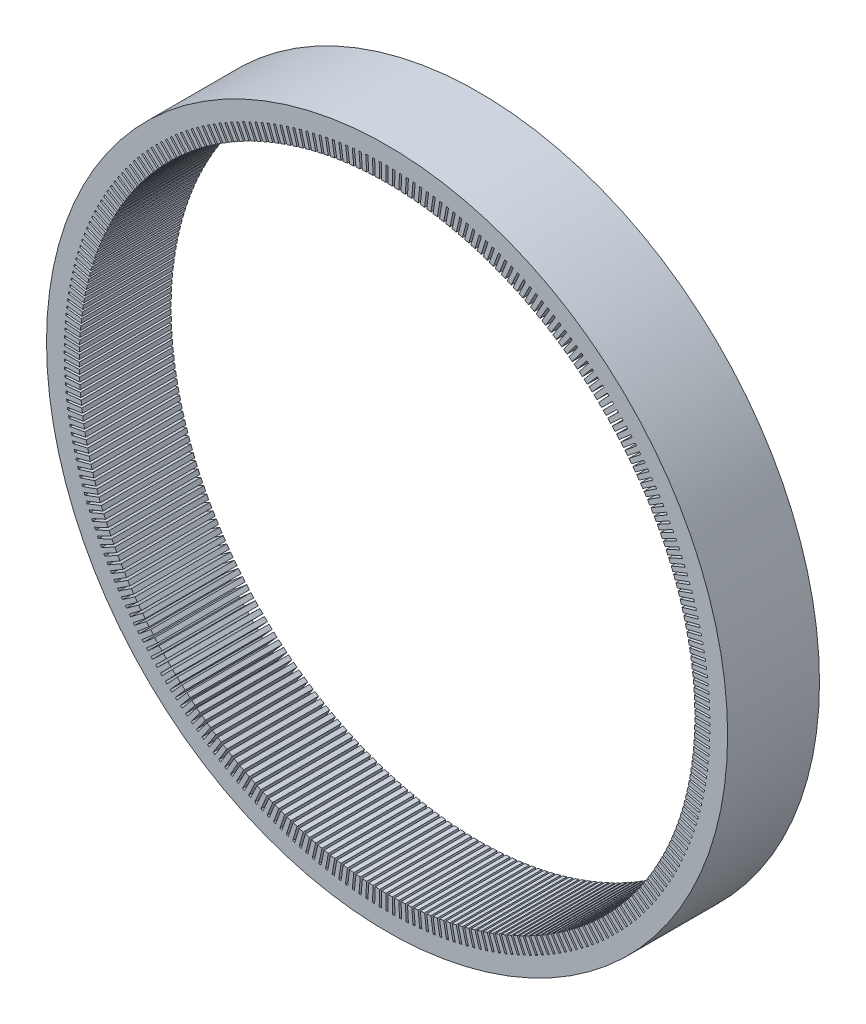
SolidWorks part; units mm, degrees
material "1023 Carbon Steel Sheet (SS)"
ref_plane "Front Plane" through (0, 0, 0) normal (0, 0, 1) x (1, 0, 0)
ref_plane "Top Plane" through (0, 0, 0) normal (0, 1, 0) x (1, 0, 0)
ref_plane "Right Plane" through (0, 0, 0) normal (1, 0, 0) x (0, 0, -1)
sketch "Sketch1" plane through (0, 0, 0) normal (0, 0, 1) x (1, 0, 0)
  line L0 (-11, 3098.7805) -> (-11, 3250.7805)
  line L1 (-11, 3250.7805) -> (11, 3250.7805)
  line L2 (11, 3250.7805) -> (11, 3098.7805)
  line L3 (57.0816, 3250.2979) -> (79.0768, 3249.8372)
  line L4 (53.8984, 3098.3312) -> (57.0816, 3250.2979)
  line L5 (79.0768, 3249.8372) -> (75.8935, 3097.8705)
  line L6 (125.1382, 3248.3896) -> (147.1189, 3247.4684)
  line L7 (118.7731, 3096.523) -> (125.1382, 3248.3896)
  line L8 (147.1189, 3247.4684) -> (140.7538, 3095.6017)
  line L9 (193.1399, 3245.0565) -> (215.0965, 3243.6751)
  line L10 (183.5957, 3093.3564) -> (193.1399, 3245.0565)
  line L11 (215.0965, 3243.6751) -> (205.5523, 3091.975)
  line L12 (261.0569, 3240.3) -> (282.9797, 3238.4591)
  line L13 (248.3378, 3088.8331) -> (261.0569, 3240.3)
  line L14 (282.9797, 3238.4591) -> (270.2607, 3086.9922)
  line L15 (328.8593, 3234.1222) -> (350.7388, 3231.8225)
  line L16 (312.971, 3082.9548) -> (328.8593, 3234.1222)
  line L17 (350.7388, 3231.8225) -> (334.8505, 3080.6552)
  line L18 (396.5176, 3226.5258) -> (418.3441, 3223.7684)
  line L19 (377.4669, 3075.7243) -> (396.5176, 3226.5258)
  line L20 (418.3441, 3223.7684) -> (399.2934, 3072.967)
  line L21 (464.0019, 3217.5141) -> (485.7659, 3214.3003)
  line L22 (441.7972, 3067.1447) -> (464.0019, 3217.5141)
  line L23 (485.7659, 3214.3003) -> (463.5612, 3063.9309)
  line L24 (531.2826, 3207.0911) -> (552.9745, 3203.4222)
  line L25 (505.9338, 3057.2197) -> (531.2826, 3207.0911)
  line L26 (552.9745, 3203.4222) -> (527.6257, 3053.5508)
  line L27 (598.3304, 3195.2614) -> (619.9407, 3191.139)
  line L28 (569.8484, 3045.9537) -> (598.3304, 3195.2614)
  line L29 (619.9407, 3191.139) -> (591.4587, 3041.8314)
  line L30 (665.1156, 3182.0302) -> (686.6349, 3177.4561)
  line L31 (633.5131, 3033.3517) -> (665.1156, 3182.0302)
  line L32 (686.6349, 3177.4561) -> (655.0323, 3028.7777)
  line L33 (731.6092, 3167.4031) -> (753.0279, 3162.3794)
  line L34 (696.8999, 3019.4192) -> (731.6092, 3167.4031)
  line L35 (753.0279, 3162.3794) -> (718.3186, 3014.3954)
  line L36 (797.7818, 3151.3868) -> (819.0906, 3145.9156)
  line L37 (759.981, 3004.1622) -> (797.7818, 3151.3868)
  line L38 (819.0906, 3145.9156) -> (781.2898, 2998.691)
  line L39 (863.6045, 3133.9882) -> (884.7941, 3128.0719)
  line L40 (822.7287, 2987.5875) -> (863.6045, 3133.9882)
  line L41 (884.7941, 3128.0719) -> (843.9183, 2981.6712)
  line L42 (929.0484, 3115.2149) -> (950.1094, 3108.8562)
  line L43 (885.1156, 2969.7023) -> (929.0484, 3115.2149)
  line L44 (950.1094, 3108.8562) -> (906.1766, 2963.3436)
  line L45 (994.0848, 3095.0751) -> (1015.008, 3088.2768)
  line L46 (947.1142, 2950.5146) -> (994.0848, 3095.0751)
  line L47 (1015.008, 3088.2768) -> (968.0375, 2943.7162)
  line L48 (1058.6851, 3073.5778) -> (1079.4614, 3066.3427)
  line L49 (1008.6974, 2930.0326) -> (1058.6851, 3073.5778)
  line L50 (1079.4614, 3066.3427) -> (1029.4737, 2922.7975)
  line L51 (1122.8211, 3050.7323) -> (1143.4413, 3043.0637)
  line L52 (1069.8382, 2908.2654) -> (1122.8211, 3050.7323)
  line L53 (1143.4413, 3043.0637) -> (1090.4584, 2900.5968)
  line L54 (1186.4646, 3026.5486) -> (1206.9197, 3018.4499)
  line L55 (1130.5096, 2885.2226) -> (1186.4646, 3026.5486)
  line L56 (1206.9197, 3018.4499) -> (1150.9647, 2877.1239)
  line L57 (1249.5876, 3001.0374) -> (1269.8686, 2992.5121)
  line L58 (1190.6852, 2860.9142) -> (1249.5876, 3001.0374)
  line L59 (1269.8686, 2992.5121) -> (1210.9662, 2852.3889)
  line L60 (1312.1625, 2974.2098) -> (1332.2605, 2965.2616)
  line L61 (1250.3386, 2835.3509) -> (1312.1625, 2974.2098)
  line L62 (1332.2605, 2965.2616) -> (1270.4366, 2826.4027)
  line L63 (1374.1619, 2946.0777) -> (1394.0681, 2936.7105)
  line L64 (1309.4435, 2808.544) -> (1374.1619, 2946.0777)
  line L65 (1394.0681, 2936.7105) -> (1329.3497, 2799.1768)
  line L66 (1435.5585, 2916.6533) -> (1455.2642, 2906.8713)
  line L67 (1367.974, 2780.5051) -> (1435.5585, 2916.6533)
  line L68 (1455.2642, 2906.8713) -> (1387.6796, 2770.7231)
  line L69 (1496.3255, 2885.9495) -> (1515.8219, 2875.757)
  line L70 (1425.9045, 2751.2466) -> (1496.3255, 2885.9495)
  line L71 (1515.8219, 2875.757) -> (1445.4009, 2741.0541)
  line L72 (1556.4361, 2853.9799) -> (1575.7148, 2843.3814)
  line L73 (1483.2095, 2720.7813) -> (1556.4361, 2853.9799)
  line L74 (1575.7148, 2843.3814) -> (1502.4883, 2710.1827)
  line L75 (1615.864, 2820.7585) -> (1634.9165, 2809.7585)
  line L76 (1539.864, 2689.1226) -> (1615.864, 2820.7585)
  line L77 (1634.9165, 2809.7585) -> (1558.9165, 2678.1226)
  line L78 (1674.5831, 2786.2997) -> (1693.4011, 2774.9031)
  line L79 (1595.843, 2656.2844) -> (1674.5831, 2786.2997)
  line L80 (1693.4011, 2774.9031) -> (1614.661, 2644.8878)
  line L81 (1732.5677, 2750.6188) -> (1751.1429, 2738.8306)
  line L82 (1651.122, 2622.281) -> (1732.5677, 2750.6188)
  line L83 (1751.1429, 2738.8306) -> (1669.6972, 2610.4928)
  line L84 (1789.7923, 2713.7314) -> (1808.1166, 2701.5568)
  line L85 (1705.6768, 2587.1274) -> (1789.7923, 2713.7314)
  line L86 (1808.1166, 2701.5568) -> (1724.0011, 2574.9528)
  line L87 (1846.2319, 2675.6537) -> (1864.2972, 2663.098)
  line L88 (1759.4834, 2550.839) -> (1846.2319, 2675.6537)
  line L89 (1864.2972, 2663.098) -> (1777.5487, 2538.2833)
  line L90 (1901.8616, 2636.4023) -> (1919.66, 2623.471)
  line L91 (1812.5183, 2513.4317) -> (1901.8616, 2636.4023)
  line L92 (1919.66, 2623.471) -> (1830.3167, 2500.5004)
  line L93 (1956.6572, 2595.9945) -> (1974.1808, 2582.6933)
  line L94 (1864.7581, 2474.9219) -> (1956.6572, 2595.9945)
  line L95 (1974.1808, 2582.6933) -> (1882.2818, 2461.6208)
  line L96 (2010.5944, 2554.448) -> (2027.8357, 2540.7828)
  line L97 (1916.18, 2435.3266) -> (2010.5944, 2554.448)
  line L98 (2027.8357, 2540.7828) -> (1933.4212, 2421.6614)
  line L99 (2063.6498, 2511.7811) -> (2080.6011, 2497.7577)
  line L100 (1966.7614, 2394.6631) -> (2063.6498, 2511.7811)
  line L101 (2080.6011, 2497.7577) -> (1983.7127, 2380.6397)
  line L102 (2115.8, 2468.0124) -> (2132.4539, 2453.6371)
  line L103 (2016.4801, 2352.9491) -> (2115.8, 2468.0124)
  line L104 (2132.4539, 2453.6371) -> (2033.134, 2338.5739)
  line L105 (2167.0221, 2423.1611) -> (2183.3713, 2408.4403)
  line L106 (2065.3143, 2310.2031) -> (2167.0221, 2423.1611)
  line L107 (2183.3713, 2408.4403) -> (2081.6635, 2295.4822)
  line L108 (2217.2937, 2377.247) -> (2233.331, 2362.187)
  line L109 (2113.2426, 2266.4438) -> (2217.2937, 2377.247)
  line L110 (2233.331, 2362.187) -> (2129.2799, 2251.3837)
  line L111 (2266.5927, 2330.2901) -> (2282.3111, 2314.8975)
  line L112 (2160.2439, 2221.6903) -> (2266.5927, 2330.2901)
  line L113 (2282.3111, 2314.8975) -> (2175.9623, 2206.2977)
  line L114 (2314.8975, 2282.3111) -> (2330.2901, 2266.5927)
  line L115 (2206.2977, 2175.9623) -> (2314.8975, 2282.3111)
  line L116 (2330.2901, 2266.5927) -> (2221.6903, 2160.2439)
  line L117 (2362.187, 2233.331) -> (2377.247, 2217.2937)
  line L118 (2251.3837, 2129.2799) -> (2362.187, 2233.331)
  line L119 (2377.247, 2217.2937) -> (2266.4438, 2113.2426)
  line L120 (2408.4403, 2183.3713) -> (2423.1611, 2167.0221)
  line L121 (2295.4822, 2081.6635) -> (2408.4403, 2183.3713)
  line L122 (2423.1611, 2167.0221) -> (2310.2031, 2065.3143)
  line L123 (2453.6371, 2132.4539) -> (2468.0124, 2115.8)
  line L124 (2338.5739, 2033.134) -> (2453.6371, 2132.4539)
  line L125 (2468.0124, 2115.8) -> (2352.9491, 2016.4801)
  line L126 (2497.7577, 2080.6011) -> (2511.7811, 2063.6498)
  line L127 (2380.6397, 1983.7127) -> (2497.7577, 2080.6011)
  line L128 (2511.7811, 2063.6498) -> (2394.6631, 1966.7614)
  line L129 (2540.7828, 2027.8357) -> (2554.448, 2010.5944)
  line L130 (2421.6614, 1933.4212) -> (2540.7828, 2027.8357)
  line L131 (2554.448, 2010.5944) -> (2435.3266, 1916.18)
  line L132 (2582.6933, 1974.1808) -> (2595.9945, 1956.6572)
  line L133 (2461.6208, 1882.2818) -> (2582.6933, 1974.1808)
  line L134 (2595.9945, 1956.6572) -> (2474.9219, 1864.7581)
  line L135 (2623.471, 1919.66) -> (2636.4023, 1901.8616)
  line L136 (2500.5004, 1830.3167) -> (2623.471, 1919.66)
  line L137 (2636.4023, 1901.8616) -> (2513.4317, 1812.5183)
  line L138 (2663.098, 1864.2972) -> (2675.6537, 1846.2319)
  line L139 (2538.2833, 1777.5487) -> (2663.098, 1864.2972)
  line L140 (2675.6537, 1846.2319) -> (2550.839, 1759.4834)
  line L141 (2701.5568, 1808.1166) -> (2713.7314, 1789.7923)
  line L142 (2574.9528, 1724.0011) -> (2701.5568, 1808.1166)
  line L143 (2713.7314, 1789.7923) -> (2587.1274, 1705.6768)
  line L144 (2738.8306, 1751.1429) -> (2750.6188, 1732.5677)
  line L145 (2610.4928, 1669.6972) -> (2738.8306, 1751.1429)
  line L146 (2750.6188, 1732.5677) -> (2622.281, 1651.122)
  line L147 (2774.9031, 1693.4011) -> (2786.2997, 1674.5831)
  line L148 (2644.8878, 1614.661) -> (2774.9031, 1693.4011)
  line L149 (2786.2997, 1674.5831) -> (2656.2844, 1595.843)
  line L150 (2809.7585, 1634.9165) -> (2820.7585, 1615.864)
  line L151 (2678.1226, 1558.9165) -> (2809.7585, 1634.9165)
  line L152 (2820.7585, 1615.864) -> (2689.1226, 1539.864)
  line L153 (2843.3814, 1575.7148) -> (2853.9799, 1556.4361)
  line L154 (2710.1827, 1502.4883) -> (2843.3814, 1575.7148)
  line L155 (2853.9799, 1556.4361) -> (2720.7813, 1483.2095)
  line L156 (2875.757, 1515.8219) -> (2885.9495, 1496.3255)
  line L157 (2741.0541, 1445.4009) -> (2875.757, 1515.8219)
  line L158 (2885.9495, 1496.3255) -> (2751.2466, 1425.9045)
  line L159 (2906.8713, 1455.2642) -> (2916.6533, 1435.5585)
  line L160 (2770.7231, 1387.6796) -> (2906.8713, 1455.2642)
  line L161 (2916.6533, 1435.5585) -> (2780.5051, 1367.974)
  line L162 (2936.7105, 1394.0681) -> (2946.0777, 1374.1619)
  line L163 (2799.1768, 1329.3497) -> (2936.7105, 1394.0681)
  line L164 (2946.0777, 1374.1619) -> (2808.544, 1309.4435)
  line L165 (2965.2616, 1332.2605) -> (2974.2098, 1312.1625)
  line L166 (2826.4027, 1270.4366) -> (2965.2616, 1332.2605)
  line L167 (2974.2098, 1312.1625) -> (2835.3509, 1250.3386)
  line L168 (2992.5121, 1269.8686) -> (3001.0374, 1249.5876)
  line L169 (2852.3889, 1210.9662) -> (2992.5121, 1269.8686)
  line L170 (3001.0374, 1249.5876) -> (2860.9142, 1190.6852)
  line L171 (3018.4499, 1206.9197) -> (3026.5486, 1186.4646)
  line L172 (2877.1239, 1150.9647) -> (3018.4499, 1206.9197)
  line L173 (3026.5486, 1186.4646) -> (2885.2226, 1130.5096)
  line L174 (3043.0637, 1143.4413) -> (3050.7323, 1122.8211)
  line L175 (2900.5968, 1090.4584) -> (3043.0637, 1143.4413)
  line L176 (3050.7323, 1122.8211) -> (2908.2654, 1069.8382)
  line L177 (3066.3427, 1079.4614) -> (3073.5778, 1058.6851)
  line L178 (2922.7975, 1029.4737) -> (3066.3427, 1079.4614)
  line L179 (3073.5778, 1058.6851) -> (2930.0326, 1008.6974)
  line L180 (3088.2768, 1015.008) -> (3095.0751, 994.0848)
  line L181 (2943.7162, 968.0375) -> (3088.2768, 1015.008)
  line L182 (3095.0751, 994.0848) -> (2950.5146, 947.1142)
  line L183 (3108.8562, 950.1094) -> (3115.2149, 929.0484)
  line L184 (2963.3436, 906.1766) -> (3108.8562, 950.1094)
  line L185 (3115.2149, 929.0484) -> (2969.7023, 885.1156)
  line L186 (3128.0719, 884.7941) -> (3133.9882, 863.6045)
  line L187 (2981.6712, 843.9183) -> (3128.0719, 884.7941)
  line L188 (3133.9882, 863.6045) -> (2987.5875, 822.7287)
  line L189 (3145.9156, 819.0906) -> (3151.3868, 797.7818)
  line L190 (2998.691, 781.2898) -> (3145.9156, 819.0906)
  line L191 (3151.3868, 797.7818) -> (3004.1622, 759.981)
  line L192 (3162.3794, 753.0279) -> (3167.4031, 731.6092)
  line L193 (3014.3954, 718.3186) -> (3162.3794, 753.0279)
  line L194 (3167.4031, 731.6092) -> (3019.4192, 696.8999)
  line L195 (3177.4561, 686.6349) -> (3182.0302, 665.1156)
  line L196 (3028.7777, 655.0323) -> (3177.4561, 686.6349)
  line L197 (3182.0302, 665.1156) -> (3033.3517, 633.5131)
  line L198 (3191.139, 619.9407) -> (3195.2614, 598.3304)
  line L199 (3041.8314, 591.4587) -> (3191.139, 619.9407)
  line L200 (3195.2614, 598.3304) -> (3045.9537, 569.8484)
  line L201 (3203.4222, 552.9745) -> (3207.0911, 531.2826)
  line L202 (3053.5508, 527.6257) -> (3203.4222, 552.9745)
  line L203 (3207.0911, 531.2826) -> (3057.2197, 505.9338)
  line L204 (3214.3003, 485.7659) -> (3217.5141, 464.0019)
  line L205 (3063.9309, 463.5612) -> (3214.3003, 485.7659)
  line L206 (3217.5141, 464.0019) -> (3067.1447, 441.7972)
  line L207 (3223.7684, 418.3441) -> (3226.5258, 396.5176)
  line L208 (3072.967, 399.2934) -> (3223.7684, 418.3441)
  line L209 (3226.5258, 396.5176) -> (3075.7243, 377.4669)
  line L210 (3231.8225, 350.7388) -> (3234.1222, 328.8593)
  line L211 (3080.6552, 334.8505) -> (3231.8225, 350.7388)
  line L212 (3234.1222, 328.8593) -> (3082.9548, 312.971)
  line L213 (3238.4591, 282.9797) -> (3240.3, 261.0569)
  line L214 (3086.9922, 270.2607) -> (3238.4591, 282.9797)
  line L215 (3240.3, 261.0569) -> (3088.8331, 248.3378)
  line L216 (3243.6751, 215.0965) -> (3245.0565, 193.1399)
  line L217 (3091.975, 205.5523) -> (3243.6751, 215.0965)
  line L218 (3245.0565, 193.1399) -> (3093.3564, 183.5957)
  line L219 (3247.4684, 147.1189) -> (3248.3896, 125.1382)
  line L220 (3095.6017, 140.7538) -> (3247.4684, 147.1189)
  line L221 (3248.3896, 125.1382) -> (3096.523, 118.7731)
  line L222 (3249.8372, 79.0768) -> (3250.2979, 57.0816)
  line L223 (3097.8705, 75.8935) -> (3249.8372, 79.0768)
  line L224 (3250.2979, 57.0816) -> (3098.3312, 53.8984)
  line L225 (3250.7805, 11) -> (3250.7805, -11)
  line L226 (3098.7805, 11) -> (3250.7805, 11)
  line L227 (3250.7805, -11) -> (3098.7805, -11)
  line L228 (3250.2979, -57.0816) -> (3249.8372, -79.0768)
  line L229 (3098.3312, -53.8984) -> (3250.2979, -57.0816)
  line L230 (3249.8372, -79.0768) -> (3097.8705, -75.8935)
  line L231 (3248.3896, -125.1382) -> (3247.4684, -147.1189)
  line L232 (3096.523, -118.7731) -> (3248.3896, -125.1382)
  line L233 (3247.4684, -147.1189) -> (3095.6017, -140.7538)
  line L234 (3245.0565, -193.1399) -> (3243.6751, -215.0965)
  line L235 (3093.3564, -183.5957) -> (3245.0565, -193.1399)
  line L236 (3243.6751, -215.0965) -> (3091.975, -205.5523)
  line L237 (3240.3, -261.0569) -> (3238.4591, -282.9797)
  line L238 (3088.8331, -248.3378) -> (3240.3, -261.0569)
  line L239 (3238.4591, -282.9797) -> (3086.9922, -270.2607)
  line L240 (3234.1222, -328.8593) -> (3231.8225, -350.7388)
  line L241 (3082.9548, -312.971) -> (3234.1222, -328.8593)
  line L242 (3231.8225, -350.7388) -> (3080.6552, -334.8505)
  line L243 (3226.5258, -396.5176) -> (3223.7684, -418.3441)
  line L244 (3075.7243, -377.4669) -> (3226.5258, -396.5176)
  line L245 (3223.7684, -418.3441) -> (3072.967, -399.2934)
  line L246 (3217.5141, -464.0019) -> (3214.3003, -485.7659)
  line L247 (3067.1447, -441.7972) -> (3217.5141, -464.0019)
  line L248 (3214.3003, -485.7659) -> (3063.9309, -463.5612)
  line L249 (3207.0911, -531.2826) -> (3203.4222, -552.9745)
  line L250 (3057.2197, -505.9338) -> (3207.0911, -531.2826)
  line L251 (3203.4222, -552.9745) -> (3053.5508, -527.6257)
  line L252 (3195.2614, -598.3304) -> (3191.139, -619.9407)
  line L253 (3045.9537, -569.8484) -> (3195.2614, -598.3304)
  line L254 (3191.139, -619.9407) -> (3041.8314, -591.4587)
  line L255 (3182.0302, -665.1156) -> (3177.4561, -686.6349)
  line L256 (3033.3517, -633.5131) -> (3182.0302, -665.1156)
  line L257 (3177.4561, -686.6349) -> (3028.7777, -655.0323)
  line L258 (3167.4031, -731.6092) -> (3162.3794, -753.0279)
  line L259 (3019.4192, -696.8999) -> (3167.4031, -731.6092)
  line L260 (3162.3794, -753.0279) -> (3014.3954, -718.3186)
  line L261 (3151.3868, -797.7818) -> (3145.9156, -819.0906)
  line L262 (3004.1622, -759.981) -> (3151.3868, -797.7818)
  line L263 (3145.9156, -819.0906) -> (2998.691, -781.2898)
  line L264 (3133.9882, -863.6045) -> (3128.0719, -884.7941)
  line L265 (2987.5875, -822.7287) -> (3133.9882, -863.6045)
  line L266 (3128.0719, -884.7941) -> (2981.6712, -843.9183)
  line L267 (3115.2149, -929.0484) -> (3108.8562, -950.1094)
  line L268 (2969.7023, -885.1156) -> (3115.2149, -929.0484)
  line L269 (3108.8562, -950.1094) -> (2963.3436, -906.1766)
  line L270 (3095.0751, -994.0848) -> (3088.2768, -1015.008)
  line L271 (2950.5146, -947.1142) -> (3095.0751, -994.0848)
  line L272 (3088.2768, -1015.008) -> (2943.7162, -968.0375)
  line L273 (3073.5778, -1058.6851) -> (3066.3427, -1079.4614)
  line L274 (2930.0326, -1008.6974) -> (3073.5778, -1058.6851)
  line L275 (3066.3427, -1079.4614) -> (2922.7975, -1029.4737)
  line L276 (3050.7323, -1122.8211) -> (3043.0637, -1143.4413)
  line L277 (2908.2654, -1069.8382) -> (3050.7323, -1122.8211)
  line L278 (3043.0637, -1143.4413) -> (2900.5968, -1090.4584)
  line L279 (3026.5486, -1186.4646) -> (3018.4499, -1206.9197)
  line L280 (2885.2226, -1130.5096) -> (3026.5486, -1186.4646)
  line L281 (3018.4499, -1206.9197) -> (2877.1239, -1150.9647)
  line L282 (3001.0374, -1249.5876) -> (2992.5121, -1269.8686)
  line L283 (2860.9142, -1190.6852) -> (3001.0374, -1249.5876)
  line L284 (2992.5121, -1269.8686) -> (2852.3889, -1210.9662)
  line L285 (2974.2098, -1312.1625) -> (2965.2616, -1332.2605)
  line L286 (2835.3509, -1250.3386) -> (2974.2098, -1312.1625)
  line L287 (2965.2616, -1332.2605) -> (2826.4027, -1270.4366)
  line L288 (2946.0777, -1374.1619) -> (2936.7105, -1394.0681)
  line L289 (2808.544, -1309.4435) -> (2946.0777, -1374.1619)
  line L290 (2936.7105, -1394.0681) -> (2799.1768, -1329.3497)
  line L291 (2916.6533, -1435.5585) -> (2906.8713, -1455.2642)
  line L292 (2780.5051, -1367.974) -> (2916.6533, -1435.5585)
  line L293 (2906.8713, -1455.2642) -> (2770.7231, -1387.6796)
  line L294 (2885.9495, -1496.3255) -> (2875.757, -1515.8219)
  line L295 (2751.2466, -1425.9045) -> (2885.9495, -1496.3255)
  line L296 (2875.757, -1515.8219) -> (2741.0541, -1445.4009)
  line L297 (2853.9799, -1556.4361) -> (2843.3814, -1575.7148)
  line L298 (2720.7813, -1483.2095) -> (2853.9799, -1556.4361)
  line L299 (2843.3814, -1575.7148) -> (2710.1827, -1502.4883)
  line L300 (2820.7585, -1615.864) -> (2809.7585, -1634.9165)
  line L301 (2689.1226, -1539.864) -> (2820.7585, -1615.864)
  line L302 (2809.7585, -1634.9165) -> (2678.1226, -1558.9165)
  line L303 (2786.2997, -1674.5831) -> (2774.9031, -1693.4011)
  line L304 (2656.2844, -1595.843) -> (2786.2997, -1674.5831)
  line L305 (2774.9031, -1693.4011) -> (2644.8878, -1614.661)
  line L306 (2750.6188, -1732.5677) -> (2738.8306, -1751.1429)
  line L307 (2622.281, -1651.122) -> (2750.6188, -1732.5677)
  line L308 (2738.8306, -1751.1429) -> (2610.4928, -1669.6972)
  line L309 (2713.7314, -1789.7923) -> (2701.5568, -1808.1166)
  line L310 (2587.1274, -1705.6768) -> (2713.7314, -1789.7923)
  line L311 (2701.5568, -1808.1166) -> (2574.9528, -1724.0011)
  line L312 (2675.6537, -1846.2319) -> (2663.098, -1864.2972)
  line L313 (2550.839, -1759.4834) -> (2675.6537, -1846.2319)
  line L314 (2663.098, -1864.2972) -> (2538.2833, -1777.5487)
  line L315 (2636.4023, -1901.8616) -> (2623.471, -1919.66)
  line L316 (2513.4317, -1812.5183) -> (2636.4023, -1901.8616)
  line L317 (2623.471, -1919.66) -> (2500.5004, -1830.3167)
  line L318 (2595.9945, -1956.6572) -> (2582.6933, -1974.1808)
  line L319 (2474.9219, -1864.7581) -> (2595.9945, -1956.6572)
  line L320 (2582.6933, -1974.1808) -> (2461.6208, -1882.2818)
  line L321 (2554.448, -2010.5944) -> (2540.7828, -2027.8357)
  line L322 (2435.3266, -1916.18) -> (2554.448, -2010.5944)
  line L323 (2540.7828, -2027.8357) -> (2421.6614, -1933.4212)
  line L324 (2511.7811, -2063.6498) -> (2497.7577, -2080.6011)
  line L325 (2394.6631, -1966.7614) -> (2511.7811, -2063.6498)
  line L326 (2497.7577, -2080.6011) -> (2380.6397, -1983.7127)
  line L327 (2468.0124, -2115.8) -> (2453.6371, -2132.4539)
  line L328 (2352.9491, -2016.4801) -> (2468.0124, -2115.8)
  line L329 (2453.6371, -2132.4539) -> (2338.5739, -2033.134)
  line L330 (2423.1611, -2167.0221) -> (2408.4403, -2183.3713)
  line L331 (2310.2031, -2065.3143) -> (2423.1611, -2167.0221)
  line L332 (2408.4403, -2183.3713) -> (2295.4822, -2081.6635)
  line L333 (2377.247, -2217.2937) -> (2362.187, -2233.331)
  line L334 (2266.4438, -2113.2426) -> (2377.247, -2217.2937)
  line L335 (2362.187, -2233.331) -> (2251.3837, -2129.2799)
  line L336 (2330.2901, -2266.5927) -> (2314.8975, -2282.3111)
  line L337 (2221.6903, -2160.2439) -> (2330.2901, -2266.5927)
  line L338 (2314.8975, -2282.3111) -> (2206.2977, -2175.9623)
  line L339 (2282.3111, -2314.8975) -> (2266.5927, -2330.2901)
  line L340 (2175.9623, -2206.2977) -> (2282.3111, -2314.8975)
  line L341 (2266.5927, -2330.2901) -> (2160.2439, -2221.6903)
  line L342 (2233.331, -2362.187) -> (2217.2937, -2377.247)
  line L343 (2129.2799, -2251.3837) -> (2233.331, -2362.187)
  line L344 (2217.2937, -2377.247) -> (2113.2426, -2266.4438)
  line L345 (2183.3713, -2408.4403) -> (2167.0221, -2423.1611)
  line L346 (2081.6635, -2295.4822) -> (2183.3713, -2408.4403)
  line L347 (2167.0221, -2423.1611) -> (2065.3143, -2310.2031)
  line L348 (2132.4539, -2453.6371) -> (2115.8, -2468.0124)
  line L349 (2033.134, -2338.5739) -> (2132.4539, -2453.6371)
  line L350 (2115.8, -2468.0124) -> (2016.4801, -2352.9491)
  line L351 (2080.6011, -2497.7577) -> (2063.6498, -2511.7811)
  line L352 (1983.7127, -2380.6397) -> (2080.6011, -2497.7577)
  line L353 (2063.6498, -2511.7811) -> (1966.7614, -2394.6631)
  line L354 (2027.8357, -2540.7828) -> (2010.5944, -2554.448)
  line L355 (1933.4212, -2421.6614) -> (2027.8357, -2540.7828)
  line L356 (2010.5944, -2554.448) -> (1916.18, -2435.3266)
  line L357 (1974.1808, -2582.6933) -> (1956.6572, -2595.9945)
  line L358 (1882.2818, -2461.6208) -> (1974.1808, -2582.6933)
  line L359 (1956.6572, -2595.9945) -> (1864.7581, -2474.9219)
  line L360 (1919.66, -2623.471) -> (1901.8616, -2636.4023)
  line L361 (1830.3167, -2500.5004) -> (1919.66, -2623.471)
  line L362 (1901.8616, -2636.4023) -> (1812.5183, -2513.4317)
  line L363 (1864.2972, -2663.098) -> (1846.2319, -2675.6537)
  line L364 (1777.5487, -2538.2833) -> (1864.2972, -2663.098)
  line L365 (1846.2319, -2675.6537) -> (1759.4834, -2550.839)
  line L366 (1808.1166, -2701.5568) -> (1789.7923, -2713.7314)
  line L367 (1724.0011, -2574.9528) -> (1808.1166, -2701.5568)
  line L368 (1789.7923, -2713.7314) -> (1705.6768, -2587.1274)
  line L369 (1751.1429, -2738.8306) -> (1732.5677, -2750.6188)
  line L370 (1669.6972, -2610.4928) -> (1751.1429, -2738.8306)
  line L371 (1732.5677, -2750.6188) -> (1651.122, -2622.281)
  line L372 (1693.4011, -2774.9031) -> (1674.5831, -2786.2997)
  line L373 (1614.661, -2644.8878) -> (1693.4011, -2774.9031)
  line L374 (1674.5831, -2786.2997) -> (1595.843, -2656.2844)
  line L375 (1634.9165, -2809.7585) -> (1615.864, -2820.7585)
  line L376 (1558.9165, -2678.1226) -> (1634.9165, -2809.7585)
  line L377 (1615.864, -2820.7585) -> (1539.864, -2689.1226)
  line L378 (1575.7148, -2843.3814) -> (1556.4361, -2853.9799)
  line L379 (1502.4883, -2710.1827) -> (1575.7148, -2843.3814)
  line L380 (1556.4361, -2853.9799) -> (1483.2095, -2720.7813)
  line L381 (1515.8219, -2875.757) -> (1496.3255, -2885.9495)
  line L382 (1445.4009, -2741.0541) -> (1515.8219, -2875.757)
  line L383 (1496.3255, -2885.9495) -> (1425.9045, -2751.2466)
  line L384 (1455.2642, -2906.8713) -> (1435.5585, -2916.6533)
  line L385 (1387.6796, -2770.7231) -> (1455.2642, -2906.8713)
  line L386 (1435.5585, -2916.6533) -> (1367.974, -2780.5051)
  line L387 (1394.0681, -2936.7105) -> (1374.1619, -2946.0777)
  line L388 (1329.3497, -2799.1768) -> (1394.0681, -2936.7105)
  line L389 (1374.1619, -2946.0777) -> (1309.4435, -2808.544)
  line L390 (1332.2605, -2965.2616) -> (1312.1625, -2974.2098)
  line L391 (1270.4366, -2826.4027) -> (1332.2605, -2965.2616)
  line L392 (1312.1625, -2974.2098) -> (1250.3386, -2835.3509)
  line L393 (1269.8686, -2992.5121) -> (1249.5876, -3001.0374)
  line L394 (1210.9662, -2852.3889) -> (1269.8686, -2992.5121)
  line L395 (1249.5876, -3001.0374) -> (1190.6852, -2860.9142)
  line L396 (1206.9197, -3018.4499) -> (1186.4646, -3026.5486)
  line L397 (1150.9647, -2877.1239) -> (1206.9197, -3018.4499)
  line L398 (1186.4646, -3026.5486) -> (1130.5096, -2885.2226)
  line L399 (1143.4413, -3043.0637) -> (1122.8211, -3050.7323)
  line L400 (1090.4584, -2900.5968) -> (1143.4413, -3043.0637)
  line L401 (1122.8211, -3050.7323) -> (1069.8382, -2908.2654)
  line L402 (1079.4614, -3066.3427) -> (1058.6851, -3073.5778)
  line L403 (1029.4737, -2922.7975) -> (1079.4614, -3066.3427)
  line L404 (1058.6851, -3073.5778) -> (1008.6974, -2930.0326)
  line L405 (1015.008, -3088.2768) -> (994.0848, -3095.0751)
  line L406 (968.0375, -2943.7162) -> (1015.008, -3088.2768)
  line L407 (994.0848, -3095.0751) -> (947.1142, -2950.5146)
  line L408 (950.1094, -3108.8562) -> (929.0484, -3115.2149)
  line L409 (906.1766, -2963.3436) -> (950.1094, -3108.8562)
  line L410 (929.0484, -3115.2149) -> (885.1156, -2969.7023)
  line L411 (884.7941, -3128.0719) -> (863.6045, -3133.9882)
  line L412 (843.9183, -2981.6712) -> (884.7941, -3128.0719)
  line L413 (863.6045, -3133.9882) -> (822.7287, -2987.5875)
  line L414 (819.0906, -3145.9156) -> (797.7818, -3151.3868)
  line L415 (781.2898, -2998.691) -> (819.0906, -3145.9156)
  line L416 (797.7818, -3151.3868) -> (759.981, -3004.1622)
  line L417 (753.0279, -3162.3794) -> (731.6092, -3167.4031)
  line L418 (718.3186, -3014.3954) -> (753.0279, -3162.3794)
  line L419 (731.6092, -3167.4031) -> (696.8999, -3019.4192)
  line L420 (686.6349, -3177.4561) -> (665.1156, -3182.0302)
  line L421 (655.0323, -3028.7777) -> (686.6349, -3177.4561)
  line L422 (665.1156, -3182.0302) -> (633.5131, -3033.3517)
  line L423 (619.9407, -3191.139) -> (598.3304, -3195.2614)
  line L424 (591.4587, -3041.8314) -> (619.9407, -3191.139)
  line L425 (598.3304, -3195.2614) -> (569.8484, -3045.9537)
  line L426 (552.9745, -3203.4222) -> (531.2826, -3207.0911)
  line L427 (527.6257, -3053.5508) -> (552.9745, -3203.4222)
  line L428 (531.2826, -3207.0911) -> (505.9338, -3057.2197)
  line L429 (485.7659, -3214.3003) -> (464.0019, -3217.5141)
  line L430 (463.5612, -3063.9309) -> (485.7659, -3214.3003)
  line L431 (464.0019, -3217.5141) -> (441.7972, -3067.1447)
  line L432 (418.3441, -3223.7684) -> (396.5176, -3226.5258)
  line L433 (399.2934, -3072.967) -> (418.3441, -3223.7684)
  line L434 (396.5176, -3226.5258) -> (377.4669, -3075.7243)
  line L435 (350.7388, -3231.8225) -> (328.8593, -3234.1222)
  line L436 (334.8505, -3080.6552) -> (350.7388, -3231.8225)
  line L437 (328.8593, -3234.1222) -> (312.971, -3082.9548)
  line L438 (282.9797, -3238.4591) -> (261.0569, -3240.3)
  line L439 (270.2607, -3086.9922) -> (282.9797, -3238.4591)
  line L440 (261.0569, -3240.3) -> (248.3378, -3088.8331)
  line L441 (215.0965, -3243.6751) -> (193.1399, -3245.0565)
  line L442 (205.5523, -3091.975) -> (215.0965, -3243.6751)
  line L443 (193.1399, -3245.0565) -> (183.5957, -3093.3564)
  line L444 (147.1189, -3247.4684) -> (125.1382, -3248.3896)
  line L445 (140.7538, -3095.6017) -> (147.1189, -3247.4684)
  line L446 (125.1382, -3248.3896) -> (118.7731, -3096.523)
  line L447 (79.0768, -3249.8372) -> (57.0816, -3250.2979)
  line L448 (75.8935, -3097.8705) -> (79.0768, -3249.8372)
  line L449 (57.0816, -3250.2979) -> (53.8984, -3098.3312)
  line L450 (11, -3250.7805) -> (-11, -3250.7805)
  line L451 (11, -3098.7805) -> (11, -3250.7805)
  line L452 (-11, -3250.7805) -> (-11, -3098.7805)
  line L453 (-57.0816, -3250.2979) -> (-79.0768, -3249.8372)
  line L454 (-53.8984, -3098.3312) -> (-57.0816, -3250.2979)
  line L455 (-79.0768, -3249.8372) -> (-75.8935, -3097.8705)
  line L456 (-125.1382, -3248.3896) -> (-147.1189, -3247.4684)
  line L457 (-118.7731, -3096.523) -> (-125.1382, -3248.3896)
  line L458 (-147.1189, -3247.4684) -> (-140.7538, -3095.6017)
  line L459 (-193.1399, -3245.0565) -> (-215.0965, -3243.6751)
  line L460 (-183.5957, -3093.3564) -> (-193.1399, -3245.0565)
  line L461 (-215.0965, -3243.6751) -> (-205.5523, -3091.975)
  line L462 (-261.0569, -3240.3) -> (-282.9797, -3238.4591)
  line L463 (-248.3378, -3088.8331) -> (-261.0569, -3240.3)
  line L464 (-282.9797, -3238.4591) -> (-270.2607, -3086.9922)
  line L465 (-328.8593, -3234.1222) -> (-350.7388, -3231.8225)
  line L466 (-312.971, -3082.9548) -> (-328.8593, -3234.1222)
  line L467 (-350.7388, -3231.8225) -> (-334.8505, -3080.6552)
  line L468 (-396.5176, -3226.5258) -> (-418.3441, -3223.7684)
  line L469 (-377.4669, -3075.7243) -> (-396.5176, -3226.5258)
  line L470 (-418.3441, -3223.7684) -> (-399.2934, -3072.967)
  line L471 (-464.0019, -3217.5141) -> (-485.7659, -3214.3003)
  line L472 (-441.7972, -3067.1447) -> (-464.0019, -3217.5141)
  line L473 (-485.7659, -3214.3003) -> (-463.5612, -3063.9309)
  line L474 (-531.2826, -3207.0911) -> (-552.9745, -3203.4222)
  line L475 (-505.9338, -3057.2197) -> (-531.2826, -3207.0911)
  line L476 (-552.9745, -3203.4222) -> (-527.6257, -3053.5508)
  line L477 (-598.3304, -3195.2614) -> (-619.9407, -3191.139)
  line L478 (-569.8484, -3045.9537) -> (-598.3304, -3195.2614)
  line L479 (-619.9407, -3191.139) -> (-591.4587, -3041.8314)
  line L480 (-665.1156, -3182.0302) -> (-686.6349, -3177.4561)
  line L481 (-633.5131, -3033.3517) -> (-665.1156, -3182.0302)
  line L482 (-686.6349, -3177.4561) -> (-655.0323, -3028.7777)
  line L483 (-731.6092, -3167.4031) -> (-753.0279, -3162.3794)
  line L484 (-696.8999, -3019.4192) -> (-731.6092, -3167.4031)
  line L485 (-753.0279, -3162.3794) -> (-718.3186, -3014.3954)
  line L486 (-797.7818, -3151.3868) -> (-819.0906, -3145.9156)
  line L487 (-759.981, -3004.1622) -> (-797.7818, -3151.3868)
  line L488 (-819.0906, -3145.9156) -> (-781.2898, -2998.691)
  line L489 (-863.6045, -3133.9882) -> (-884.7941, -3128.0719)
  line L490 (-822.7287, -2987.5875) -> (-863.6045, -3133.9882)
  line L491 (-884.7941, -3128.0719) -> (-843.9183, -2981.6712)
  line L492 (-929.0484, -3115.2149) -> (-950.1094, -3108.8562)
  line L493 (-885.1156, -2969.7023) -> (-929.0484, -3115.2149)
  line L494 (-950.1094, -3108.8562) -> (-906.1766, -2963.3436)
  line L495 (-994.0848, -3095.0751) -> (-1015.008, -3088.2768)
  line L496 (-947.1142, -2950.5146) -> (-994.0848, -3095.0751)
  line L497 (-1015.008, -3088.2768) -> (-968.0375, -2943.7162)
  line L498 (-1058.6851, -3073.5778) -> (-1079.4614, -3066.3427)
  line L499 (-1008.6974, -2930.0326) -> (-1058.6851, -3073.5778)
  line L500 (-1079.4614, -3066.3427) -> (-1029.4737, -2922.7975)
  line L501 (-1122.8211, -3050.7323) -> (-1143.4413, -3043.0637)
  line L502 (-1069.8382, -2908.2654) -> (-1122.8211, -3050.7323)
  line L503 (-1143.4413, -3043.0637) -> (-1090.4584, -2900.5968)
  line L504 (-1186.4646, -3026.5486) -> (-1206.9197, -3018.4499)
  line L505 (-1130.5096, -2885.2226) -> (-1186.4646, -3026.5486)
  line L506 (-1206.9197, -3018.4499) -> (-1150.9647, -2877.1239)
  line L507 (-1249.5876, -3001.0374) -> (-1269.8686, -2992.5121)
  line L508 (-1190.6852, -2860.9142) -> (-1249.5876, -3001.0374)
  line L509 (-1269.8686, -2992.5121) -> (-1210.9662, -2852.3889)
  line L510 (-1312.1625, -2974.2098) -> (-1332.2605, -2965.2616)
  line L511 (-1250.3386, -2835.3509) -> (-1312.1625, -2974.2098)
  line L512 (-1332.2605, -2965.2616) -> (-1270.4366, -2826.4027)
  line L513 (-1374.1619, -2946.0777) -> (-1394.0681, -2936.7105)
  line L514 (-1309.4435, -2808.544) -> (-1374.1619, -2946.0777)
  line L515 (-1394.0681, -2936.7105) -> (-1329.3497, -2799.1768)
  line L516 (-1435.5585, -2916.6533) -> (-1455.2642, -2906.8713)
  line L517 (-1367.974, -2780.5051) -> (-1435.5585, -2916.6533)
  line L518 (-1455.2642, -2906.8713) -> (-1387.6796, -2770.7231)
  line L519 (-1496.3255, -2885.9495) -> (-1515.8219, -2875.757)
  line L520 (-1425.9045, -2751.2466) -> (-1496.3255, -2885.9495)
  line L521 (-1515.8219, -2875.757) -> (-1445.4009, -2741.0541)
  line L522 (-1556.4361, -2853.9799) -> (-1575.7148, -2843.3814)
  line L523 (-1483.2095, -2720.7813) -> (-1556.4361, -2853.9799)
  line L524 (-1575.7148, -2843.3814) -> (-1502.4883, -2710.1827)
  line L525 (-1615.864, -2820.7585) -> (-1634.9165, -2809.7585)
  line L526 (-1539.864, -2689.1226) -> (-1615.864, -2820.7585)
  line L527 (-1634.9165, -2809.7585) -> (-1558.9165, -2678.1226)
  line L528 (-1674.5831, -2786.2997) -> (-1693.4011, -2774.9031)
  line L529 (-1595.843, -2656.2844) -> (-1674.5831, -2786.2997)
  line L530 (-1693.4011, -2774.9031) -> (-1614.661, -2644.8878)
  line L531 (-1732.5677, -2750.6188) -> (-1751.1429, -2738.8306)
  line L532 (-1651.122, -2622.281) -> (-1732.5677, -2750.6188)
  line L533 (-1751.1429, -2738.8306) -> (-1669.6972, -2610.4928)
  line L534 (-1789.7923, -2713.7314) -> (-1808.1166, -2701.5568)
  line L535 (-1705.6768, -2587.1274) -> (-1789.7923, -2713.7314)
  line L536 (-1808.1166, -2701.5568) -> (-1724.0011, -2574.9528)
  line L537 (-1846.2319, -2675.6537) -> (-1864.2972, -2663.098)
  line L538 (-1759.4834, -2550.839) -> (-1846.2319, -2675.6537)
  line L539 (-1864.2972, -2663.098) -> (-1777.5487, -2538.2833)
  line L540 (-1901.8616, -2636.4023) -> (-1919.66, -2623.471)
  line L541 (-1812.5183, -2513.4317) -> (-1901.8616, -2636.4023)
  line L542 (-1919.66, -2623.471) -> (-1830.3167, -2500.5004)
  line L543 (-1956.6572, -2595.9945) -> (-1974.1808, -2582.6933)
  line L544 (-1864.7581, -2474.9219) -> (-1956.6572, -2595.9945)
  line L545 (-1974.1808, -2582.6933) -> (-1882.2818, -2461.6208)
  line L546 (-2010.5944, -2554.448) -> (-2027.8357, -2540.7828)
  line L547 (-1916.18, -2435.3266) -> (-2010.5944, -2554.448)
  line L548 (-2027.8357, -2540.7828) -> (-1933.4212, -2421.6614)
  line L549 (-2063.6498, -2511.7811) -> (-2080.6011, -2497.7577)
  line L550 (-1966.7614, -2394.6631) -> (-2063.6498, -2511.7811)
  line L551 (-2080.6011, -2497.7577) -> (-1983.7127, -2380.6397)
  line L552 (-2115.8, -2468.0124) -> (-2132.4539, -2453.6371)
  line L553 (-2016.4801, -2352.9491) -> (-2115.8, -2468.0124)
  line L554 (-2132.4539, -2453.6371) -> (-2033.134, -2338.5739)
  line L555 (-2167.0221, -2423.1611) -> (-2183.3713, -2408.4403)
  line L556 (-2065.3143, -2310.2031) -> (-2167.0221, -2423.1611)
  line L557 (-2183.3713, -2408.4403) -> (-2081.6635, -2295.4822)
  line L558 (-2217.2937, -2377.247) -> (-2233.331, -2362.187)
  line L559 (-2113.2426, -2266.4438) -> (-2217.2937, -2377.247)
  line L560 (-2233.331, -2362.187) -> (-2129.2799, -2251.3837)
  line L561 (-2266.5927, -2330.2901) -> (-2282.3111, -2314.8975)
  line L562 (-2160.2439, -2221.6903) -> (-2266.5927, -2330.2901)
  line L563 (-2282.3111, -2314.8975) -> (-2175.9623, -2206.2977)
  line L564 (-2314.8975, -2282.3111) -> (-2330.2901, -2266.5927)
  line L565 (-2206.2977, -2175.9623) -> (-2314.8975, -2282.3111)
  line L566 (-2330.2901, -2266.5927) -> (-2221.6903, -2160.2439)
  line L567 (-2362.187, -2233.331) -> (-2377.247, -2217.2937)
  line L568 (-2251.3837, -2129.2799) -> (-2362.187, -2233.331)
  line L569 (-2377.247, -2217.2937) -> (-2266.4438, -2113.2426)
  line L570 (-2408.4403, -2183.3713) -> (-2423.1611, -2167.0221)
  line L571 (-2295.4822, -2081.6635) -> (-2408.4403, -2183.3713)
  line L572 (-2423.1611, -2167.0221) -> (-2310.2031, -2065.3143)
  line L573 (-2453.6371, -2132.4539) -> (-2468.0124, -2115.8)
  line L574 (-2338.5739, -2033.134) -> (-2453.6371, -2132.4539)
  line L575 (-2468.0124, -2115.8) -> (-2352.9491, -2016.4801)
  line L576 (-2497.7577, -2080.6011) -> (-2511.7811, -2063.6498)
  line L577 (-2380.6397, -1983.7127) -> (-2497.7577, -2080.6011)
  line L578 (-2511.7811, -2063.6498) -> (-2394.6631, -1966.7614)
  line L579 (-2540.7828, -2027.8357) -> (-2554.448, -2010.5944)
  line L580 (-2421.6614, -1933.4212) -> (-2540.7828, -2027.8357)
  line L581 (-2554.448, -2010.5944) -> (-2435.3266, -1916.18)
  line L582 (-2582.6933, -1974.1808) -> (-2595.9945, -1956.6572)
  line L583 (-2461.6208, -1882.2818) -> (-2582.6933, -1974.1808)
  line L584 (-2595.9945, -1956.6572) -> (-2474.9219, -1864.7581)
  line L585 (-2623.471, -1919.66) -> (-2636.4023, -1901.8616)
  line L586 (-2500.5004, -1830.3167) -> (-2623.471, -1919.66)
  line L587 (-2636.4023, -1901.8616) -> (-2513.4317, -1812.5183)
  line L588 (-2663.098, -1864.2972) -> (-2675.6537, -1846.2319)
  line L589 (-2538.2833, -1777.5487) -> (-2663.098, -1864.2972)
  line L590 (-2675.6537, -1846.2319) -> (-2550.839, -1759.4834)
  line L591 (-2701.5568, -1808.1166) -> (-2713.7314, -1789.7923)
  line L592 (-2574.9528, -1724.0011) -> (-2701.5568, -1808.1166)
  line L593 (-2713.7314, -1789.7923) -> (-2587.1274, -1705.6768)
  line L594 (-2738.8306, -1751.1429) -> (-2750.6188, -1732.5677)
  line L595 (-2610.4928, -1669.6972) -> (-2738.8306, -1751.1429)
  line L596 (-2750.6188, -1732.5677) -> (-2622.281, -1651.122)
  line L597 (-2774.9031, -1693.4011) -> (-2786.2997, -1674.5831)
  line L598 (-2644.8878, -1614.661) -> (-2774.9031, -1693.4011)
  line L599 (-2786.2997, -1674.5831) -> (-2656.2844, -1595.843)
  line L600 (-2809.7585, -1634.9165) -> (-2820.7585, -1615.864)
  line L601 (-2678.1226, -1558.9165) -> (-2809.7585, -1634.9165)
  line L602 (-2820.7585, -1615.864) -> (-2689.1226, -1539.864)
  line L603 (-2843.3814, -1575.7148) -> (-2853.9799, -1556.4361)
  line L604 (-2710.1827, -1502.4883) -> (-2843.3814, -1575.7148)
  line L605 (-2853.9799, -1556.4361) -> (-2720.7813, -1483.2095)
  line L606 (-2875.757, -1515.8219) -> (-2885.9495, -1496.3255)
  line L607 (-2741.0541, -1445.4009) -> (-2875.757, -1515.8219)
  line L608 (-2885.9495, -1496.3255) -> (-2751.2466, -1425.9045)
  line L609 (-2906.8713, -1455.2642) -> (-2916.6533, -1435.5585)
  line L610 (-2770.7231, -1387.6796) -> (-2906.8713, -1455.2642)
  line L611 (-2916.6533, -1435.5585) -> (-2780.5051, -1367.974)
  line L612 (-2936.7105, -1394.0681) -> (-2946.0777, -1374.1619)
  line L613 (-2799.1768, -1329.3497) -> (-2936.7105, -1394.0681)
  line L614 (-2946.0777, -1374.1619) -> (-2808.544, -1309.4435)
  line L615 (-2965.2616, -1332.2605) -> (-2974.2098, -1312.1625)
  line L616 (-2826.4027, -1270.4366) -> (-2965.2616, -1332.2605)
  line L617 (-2974.2098, -1312.1625) -> (-2835.3509, -1250.3386)
  line L618 (-2992.5121, -1269.8686) -> (-3001.0374, -1249.5876)
  line L619 (-2852.3889, -1210.9662) -> (-2992.5121, -1269.8686)
  line L620 (-3001.0374, -1249.5876) -> (-2860.9142, -1190.6852)
  line L621 (-3018.4499, -1206.9197) -> (-3026.5486, -1186.4646)
  line L622 (-2877.1239, -1150.9647) -> (-3018.4499, -1206.9197)
  line L623 (-3026.5486, -1186.4646) -> (-2885.2226, -1130.5096)
  line L624 (-3043.0637, -1143.4413) -> (-3050.7323, -1122.8211)
  line L625 (-2900.5968, -1090.4584) -> (-3043.0637, -1143.4413)
  line L626 (-3050.7323, -1122.8211) -> (-2908.2654, -1069.8382)
  line L627 (-3066.3427, -1079.4614) -> (-3073.5778, -1058.6851)
  line L628 (-2922.7975, -1029.4737) -> (-3066.3427, -1079.4614)
  line L629 (-3073.5778, -1058.6851) -> (-2930.0326, -1008.6974)
  line L630 (-3088.2768, -1015.008) -> (-3095.0751, -994.0848)
  line L631 (-2943.7162, -968.0375) -> (-3088.2768, -1015.008)
  line L632 (-3095.0751, -994.0848) -> (-2950.5146, -947.1142)
  line L633 (-3108.8562, -950.1094) -> (-3115.2149, -929.0484)
  line L634 (-2963.3436, -906.1766) -> (-3108.8562, -950.1094)
  line L635 (-3115.2149, -929.0484) -> (-2969.7023, -885.1156)
  line L636 (-3128.0719, -884.7941) -> (-3133.9882, -863.6045)
  line L637 (-2981.6712, -843.9183) -> (-3128.0719, -884.7941)
  line L638 (-3133.9882, -863.6045) -> (-2987.5875, -822.7287)
  line L639 (-3145.9156, -819.0906) -> (-3151.3868, -797.7818)
  line L640 (-2998.691, -781.2898) -> (-3145.9156, -819.0906)
  line L641 (-3151.3868, -797.7818) -> (-3004.1622, -759.981)
  line L642 (-3162.3794, -753.0279) -> (-3167.4031, -731.6092)
  line L643 (-3014.3954, -718.3186) -> (-3162.3794, -753.0279)
  line L644 (-3167.4031, -731.6092) -> (-3019.4192, -696.8999)
  line L645 (-3177.4561, -686.6349) -> (-3182.0302, -665.1156)
  line L646 (-3028.7777, -655.0323) -> (-3177.4561, -686.6349)
  line L647 (-3182.0302, -665.1156) -> (-3033.3517, -633.5131)
  line L648 (-3191.139, -619.9407) -> (-3195.2614, -598.3304)
  line L649 (-3041.8314, -591.4587) -> (-3191.139, -619.9407)
  line L650 (-3195.2614, -598.3304) -> (-3045.9537, -569.8484)
  line L651 (-3203.4222, -552.9745) -> (-3207.0911, -531.2826)
  line L652 (-3053.5508, -527.6257) -> (-3203.4222, -552.9745)
  line L653 (-3207.0911, -531.2826) -> (-3057.2197, -505.9338)
  line L654 (-3214.3003, -485.7659) -> (-3217.5141, -464.0019)
  line L655 (-3063.9309, -463.5612) -> (-3214.3003, -485.7659)
  line L656 (-3217.5141, -464.0019) -> (-3067.1447, -441.7972)
  line L657 (-3223.7684, -418.3441) -> (-3226.5258, -396.5176)
  line L658 (-3072.967, -399.2934) -> (-3223.7684, -418.3441)
  line L659 (-3226.5258, -396.5176) -> (-3075.7243, -377.4669)
  line L660 (-3231.8225, -350.7388) -> (-3234.1222, -328.8593)
  line L661 (-3080.6552, -334.8505) -> (-3231.8225, -350.7388)
  line L662 (-3234.1222, -328.8593) -> (-3082.9548, -312.971)
  line L663 (-3238.4591, -282.9797) -> (-3240.3, -261.0569)
  line L664 (-3086.9922, -270.2607) -> (-3238.4591, -282.9797)
  line L665 (-3240.3, -261.0569) -> (-3088.8331, -248.3378)
  line L666 (-3243.6751, -215.0965) -> (-3245.0565, -193.1399)
  line L667 (-3091.975, -205.5523) -> (-3243.6751, -215.0965)
  line L668 (-3245.0565, -193.1399) -> (-3093.3564, -183.5957)
  line L669 (-3247.4684, -147.1189) -> (-3248.3896, -125.1382)
  line L670 (-3095.6017, -140.7538) -> (-3247.4684, -147.1189)
  line L671 (-3248.3896, -125.1382) -> (-3096.523, -118.7731)
  line L672 (-3249.8372, -79.0768) -> (-3250.2979, -57.0816)
  line L673 (-3097.8705, -75.8935) -> (-3249.8372, -79.0768)
  line L674 (-3250.2979, -57.0816) -> (-3098.3312, -53.8984)
  line L675 (-3250.7805, -11) -> (-3250.7805, 11)
  line L676 (-3098.7805, -11) -> (-3250.7805, -11)
  line L677 (-3250.7805, 11) -> (-3098.7805, 11)
  line L678 (-3250.2979, 57.0816) -> (-3249.8372, 79.0768)
  line L679 (-3098.3312, 53.8984) -> (-3250.2979, 57.0816)
  line L680 (-3249.8372, 79.0768) -> (-3097.8705, 75.8935)
  line L681 (-3248.3896, 125.1382) -> (-3247.4684, 147.1189)
  line L682 (-3096.523, 118.7731) -> (-3248.3896, 125.1382)
  line L683 (-3247.4684, 147.1189) -> (-3095.6017, 140.7538)
  line L684 (-3245.0565, 193.1399) -> (-3243.6751, 215.0965)
  line L685 (-3093.3564, 183.5957) -> (-3245.0565, 193.1399)
  line L686 (-3243.6751, 215.0965) -> (-3091.975, 205.5523)
  line L687 (-3240.3, 261.0569) -> (-3238.4591, 282.9797)
  line L688 (-3088.8331, 248.3378) -> (-3240.3, 261.0569)
  line L689 (-3238.4591, 282.9797) -> (-3086.9922, 270.2607)
  line L690 (-3234.1222, 328.8593) -> (-3231.8225, 350.7388)
  line L691 (-3082.9548, 312.971) -> (-3234.1222, 328.8593)
  line L692 (-3231.8225, 350.7388) -> (-3080.6552, 334.8505)
  line L693 (-3226.5258, 396.5176) -> (-3223.7684, 418.3441)
  line L694 (-3075.7243, 377.4669) -> (-3226.5258, 396.5176)
  line L695 (-3223.7684, 418.3441) -> (-3072.967, 399.2934)
  line L696 (-3217.5141, 464.0019) -> (-3214.3003, 485.7659)
  line L697 (-3067.1447, 441.7972) -> (-3217.5141, 464.0019)
  line L698 (-3214.3003, 485.7659) -> (-3063.9309, 463.5612)
  line L699 (-3207.0911, 531.2826) -> (-3203.4222, 552.9745)
  line L700 (-3057.2197, 505.9338) -> (-3207.0911, 531.2826)
  line L701 (-3203.4222, 552.9745) -> (-3053.5508, 527.6257)
  line L702 (-3195.2614, 598.3304) -> (-3191.139, 619.9407)
  line L703 (-3045.9537, 569.8484) -> (-3195.2614, 598.3304)
  line L704 (-3191.139, 619.9407) -> (-3041.8314, 591.4587)
  line L705 (-3182.0302, 665.1156) -> (-3177.4561, 686.6349)
  line L706 (-3033.3517, 633.5131) -> (-3182.0302, 665.1156)
  line L707 (-3177.4561, 686.6349) -> (-3028.7777, 655.0323)
  line L708 (-3167.4031, 731.6092) -> (-3162.3794, 753.0279)
  line L709 (-3019.4192, 696.8999) -> (-3167.4031, 731.6092)
  line L710 (-3162.3794, 753.0279) -> (-3014.3954, 718.3186)
  line L711 (-3151.3868, 797.7818) -> (-3145.9156, 819.0906)
  line L712 (-3004.1622, 759.981) -> (-3151.3868, 797.7818)
  line L713 (-3145.9156, 819.0906) -> (-2998.691, 781.2898)
  line L714 (-3133.9882, 863.6045) -> (-3128.0719, 884.7941)
  line L715 (-2987.5875, 822.7287) -> (-3133.9882, 863.6045)
  line L716 (-3128.0719, 884.7941) -> (-2981.6712, 843.9183)
  line L717 (-3115.2149, 929.0484) -> (-3108.8562, 950.1094)
  line L718 (-2969.7023, 885.1156) -> (-3115.2149, 929.0484)
  line L719 (-3108.8562, 950.1094) -> (-2963.3436, 906.1766)
  line L720 (-3095.0751, 994.0848) -> (-3088.2768, 1015.008)
  line L721 (-2950.5146, 947.1142) -> (-3095.0751, 994.0848)
  line L722 (-3088.2768, 1015.008) -> (-2943.7162, 968.0375)
  line L723 (-3073.5778, 1058.6851) -> (-3066.3427, 1079.4614)
  line L724 (-2930.0326, 1008.6974) -> (-3073.5778, 1058.6851)
  line L725 (-3066.3427, 1079.4614) -> (-2922.7975, 1029.4737)
  line L726 (-3050.7323, 1122.8211) -> (-3043.0637, 1143.4413)
  line L727 (-2908.2654, 1069.8382) -> (-3050.7323, 1122.8211)
  line L728 (-3043.0637, 1143.4413) -> (-2900.5968, 1090.4584)
  line L729 (-3026.5486, 1186.4646) -> (-3018.4499, 1206.9197)
  line L730 (-2885.2226, 1130.5096) -> (-3026.5486, 1186.4646)
  line L731 (-3018.4499, 1206.9197) -> (-2877.1239, 1150.9647)
  line L732 (-3001.0374, 1249.5876) -> (-2992.5121, 1269.8686)
  line L733 (-2860.9142, 1190.6852) -> (-3001.0374, 1249.5876)
  line L734 (-2992.5121, 1269.8686) -> (-2852.3889, 1210.9662)
  line L735 (-2974.2098, 1312.1625) -> (-2965.2616, 1332.2605)
  line L736 (-2835.3509, 1250.3386) -> (-2974.2098, 1312.1625)
  line L737 (-2965.2616, 1332.2605) -> (-2826.4027, 1270.4366)
  line L738 (-2946.0777, 1374.1619) -> (-2936.7105, 1394.0681)
  line L739 (-2808.544, 1309.4435) -> (-2946.0777, 1374.1619)
  line L740 (-2936.7105, 1394.0681) -> (-2799.1768, 1329.3497)
  line L741 (-2916.6533, 1435.5585) -> (-2906.8713, 1455.2642)
  line L742 (-2780.5051, 1367.974) -> (-2916.6533, 1435.5585)
  line L743 (-2906.8713, 1455.2642) -> (-2770.7231, 1387.6796)
  line L744 (-2885.9495, 1496.3255) -> (-2875.757, 1515.8219)
  line L745 (-2751.2466, 1425.9045) -> (-2885.9495, 1496.3255)
  line L746 (-2875.757, 1515.8219) -> (-2741.0541, 1445.4009)
  line L747 (-2853.9799, 1556.4361) -> (-2843.3814, 1575.7148)
  line L748 (-2720.7813, 1483.2095) -> (-2853.9799, 1556.4361)
  line L749 (-2843.3814, 1575.7148) -> (-2710.1827, 1502.4883)
  line L750 (-2820.7585, 1615.864) -> (-2809.7585, 1634.9165)
  line L751 (-2689.1226, 1539.864) -> (-2820.7585, 1615.864)
  line L752 (-2809.7585, 1634.9165) -> (-2678.1226, 1558.9165)
  line L753 (-2786.2997, 1674.5831) -> (-2774.9031, 1693.4011)
  line L754 (-2656.2844, 1595.843) -> (-2786.2997, 1674.5831)
  line L755 (-2774.9031, 1693.4011) -> (-2644.8878, 1614.661)
  line L756 (-2750.6188, 1732.5677) -> (-2738.8306, 1751.1429)
  line L757 (-2622.281, 1651.122) -> (-2750.6188, 1732.5677)
  line L758 (-2738.8306, 1751.1429) -> (-2610.4928, 1669.6972)
  line L759 (-2713.7314, 1789.7923) -> (-2701.5568, 1808.1166)
  line L760 (-2587.1274, 1705.6768) -> (-2713.7314, 1789.7923)
  line L761 (-2701.5568, 1808.1166) -> (-2574.9528, 1724.0011)
  line L762 (-2675.6537, 1846.2319) -> (-2663.098, 1864.2972)
  line L763 (-2550.839, 1759.4834) -> (-2675.6537, 1846.2319)
  line L764 (-2663.098, 1864.2972) -> (-2538.2833, 1777.5487)
  line L765 (-2636.4023, 1901.8616) -> (-2623.471, 1919.66)
  line L766 (-2513.4317, 1812.5183) -> (-2636.4023, 1901.8616)
  line L767 (-2623.471, 1919.66) -> (-2500.5004, 1830.3167)
  line L768 (-2595.9945, 1956.6572) -> (-2582.6933, 1974.1808)
  line L769 (-2474.9219, 1864.7581) -> (-2595.9945, 1956.6572)
  line L770 (-2582.6933, 1974.1808) -> (-2461.6208, 1882.2818)
  line L771 (-2554.448, 2010.5944) -> (-2540.7828, 2027.8357)
  line L772 (-2435.3266, 1916.18) -> (-2554.448, 2010.5944)
  line L773 (-2540.7828, 2027.8357) -> (-2421.6614, 1933.4212)
  line L774 (-2511.7811, 2063.6498) -> (-2497.7577, 2080.6011)
  line L775 (-2394.6631, 1966.7614) -> (-2511.7811, 2063.6498)
  line L776 (-2497.7577, 2080.6011) -> (-2380.6397, 1983.7127)
  line L777 (-2468.0124, 2115.8) -> (-2453.6371, 2132.4539)
  line L778 (-2352.9491, 2016.4801) -> (-2468.0124, 2115.8)
  line L779 (-2453.6371, 2132.4539) -> (-2338.5739, 2033.134)
  line L780 (-2423.1611, 2167.0221) -> (-2408.4403, 2183.3713)
  line L781 (-2310.2031, 2065.3143) -> (-2423.1611, 2167.0221)
  line L782 (-2408.4403, 2183.3713) -> (-2295.4822, 2081.6635)
  line L783 (-2377.247, 2217.2937) -> (-2362.187, 2233.331)
  line L784 (-2266.4438, 2113.2426) -> (-2377.247, 2217.2937)
  line L785 (-2362.187, 2233.331) -> (-2251.3837, 2129.2799)
  line L786 (-2330.2901, 2266.5927) -> (-2314.8975, 2282.3111)
  line L787 (-2221.6903, 2160.2439) -> (-2330.2901, 2266.5927)
  line L788 (-2314.8975, 2282.3111) -> (-2206.2977, 2175.9623)
  line L789 (-2282.3111, 2314.8975) -> (-2266.5927, 2330.2901)
  line L790 (-2175.9623, 2206.2977) -> (-2282.3111, 2314.8975)
  line L791 (-2266.5927, 2330.2901) -> (-2160.2439, 2221.6903)
  line L792 (-2233.331, 2362.187) -> (-2217.2937, 2377.247)
  line L793 (-2129.2799, 2251.3837) -> (-2233.331, 2362.187)
  line L794 (-2217.2937, 2377.247) -> (-2113.2426, 2266.4438)
  line L795 (-2183.3713, 2408.4403) -> (-2167.0221, 2423.1611)
  line L796 (-2081.6635, 2295.4822) -> (-2183.3713, 2408.4403)
  line L797 (-2167.0221, 2423.1611) -> (-2065.3143, 2310.2031)
  line L798 (-2132.4539, 2453.6371) -> (-2115.8, 2468.0124)
  line L799 (-2033.134, 2338.5739) -> (-2132.4539, 2453.6371)
  line L800 (-2115.8, 2468.0124) -> (-2016.4801, 2352.9491)
  line L801 (-2080.6011, 2497.7577) -> (-2063.6498, 2511.7811)
  line L802 (-1983.7127, 2380.6397) -> (-2080.6011, 2497.7577)
  line L803 (-2063.6498, 2511.7811) -> (-1966.7614, 2394.6631)
  line L804 (-2027.8357, 2540.7828) -> (-2010.5944, 2554.448)
  line L805 (-1933.4212, 2421.6614) -> (-2027.8357, 2540.7828)
  line L806 (-2010.5944, 2554.448) -> (-1916.18, 2435.3266)
  line L807 (-1974.1808, 2582.6933) -> (-1956.6572, 2595.9945)
  line L808 (-1882.2818, 2461.6208) -> (-1974.1808, 2582.6933)
  line L809 (-1956.6572, 2595.9945) -> (-1864.7581, 2474.9219)
  line L810 (-1919.66, 2623.471) -> (-1901.8616, 2636.4023)
  line L811 (-1830.3167, 2500.5004) -> (-1919.66, 2623.471)
  line L812 (-1901.8616, 2636.4023) -> (-1812.5183, 2513.4317)
  line L813 (-1864.2972, 2663.098) -> (-1846.2319, 2675.6537)
  line L814 (-1777.5487, 2538.2833) -> (-1864.2972, 2663.098)
  line L815 (-1846.2319, 2675.6537) -> (-1759.4834, 2550.839)
  line L816 (-1808.1166, 2701.5568) -> (-1789.7923, 2713.7314)
  line L817 (-1724.0011, 2574.9528) -> (-1808.1166, 2701.5568)
  line L818 (-1789.7923, 2713.7314) -> (-1705.6768, 2587.1274)
  line L819 (-1751.1429, 2738.8306) -> (-1732.5677, 2750.6188)
  line L820 (-1669.6972, 2610.4928) -> (-1751.1429, 2738.8306)
  line L821 (-1732.5677, 2750.6188) -> (-1651.122, 2622.281)
  line L822 (-1693.4011, 2774.9031) -> (-1674.5831, 2786.2997)
  line L823 (-1614.661, 2644.8878) -> (-1693.4011, 2774.9031)
  line L824 (-1674.5831, 2786.2997) -> (-1595.843, 2656.2844)
  line L825 (-1634.9165, 2809.7585) -> (-1615.864, 2820.7585)
  line L826 (-1558.9165, 2678.1226) -> (-1634.9165, 2809.7585)
  line L827 (-1615.864, 2820.7585) -> (-1539.864, 2689.1226)
  line L828 (-1575.7148, 2843.3814) -> (-1556.4361, 2853.9799)
  line L829 (-1502.4883, 2710.1827) -> (-1575.7148, 2843.3814)
  line L830 (-1556.4361, 2853.9799) -> (-1483.2095, 2720.7813)
  line L831 (-1515.8219, 2875.757) -> (-1496.3255, 2885.9495)
  line L832 (-1445.4009, 2741.0541) -> (-1515.8219, 2875.757)
  line L833 (-1496.3255, 2885.9495) -> (-1425.9045, 2751.2466)
  line L834 (-1455.2642, 2906.8713) -> (-1435.5585, 2916.6533)
  line L835 (-1387.6796, 2770.7231) -> (-1455.2642, 2906.8713)
  line L836 (-1435.5585, 2916.6533) -> (-1367.974, 2780.5051)
  line L837 (-1394.0681, 2936.7105) -> (-1374.1619, 2946.0777)
  line L838 (-1329.3497, 2799.1768) -> (-1394.0681, 2936.7105)
  line L839 (-1374.1619, 2946.0777) -> (-1309.4435, 2808.544)
  line L840 (-1332.2605, 2965.2616) -> (-1312.1625, 2974.2098)
  line L841 (-1270.4366, 2826.4027) -> (-1332.2605, 2965.2616)
  line L842 (-1312.1625, 2974.2098) -> (-1250.3386, 2835.3509)
  line L843 (-1269.8686, 2992.5121) -> (-1249.5876, 3001.0374)
  line L844 (-1210.9662, 2852.3889) -> (-1269.8686, 2992.5121)
  line L845 (-1249.5876, 3001.0374) -> (-1190.6852, 2860.9142)
  line L846 (-1206.9197, 3018.4499) -> (-1186.4646, 3026.5486)
  line L847 (-1150.9647, 2877.1239) -> (-1206.9197, 3018.4499)
  line L848 (-1186.4646, 3026.5486) -> (-1130.5096, 2885.2226)
  line L849 (-1143.4413, 3043.0637) -> (-1122.8211, 3050.7323)
  line L850 (-1090.4584, 2900.5968) -> (-1143.4413, 3043.0637)
  line L851 (-1122.8211, 3050.7323) -> (-1069.8382, 2908.2654)
  line L852 (-1079.4614, 3066.3427) -> (-1058.6851, 3073.5778)
  line L853 (-1029.4737, 2922.7975) -> (-1079.4614, 3066.3427)
  line L854 (-1058.6851, 3073.5778) -> (-1008.6974, 2930.0326)
  line L855 (-1015.008, 3088.2768) -> (-994.0848, 3095.0751)
  line L856 (-968.0375, 2943.7162) -> (-1015.008, 3088.2768)
  line L857 (-994.0848, 3095.0751) -> (-947.1142, 2950.5146)
  line L858 (-950.1094, 3108.8562) -> (-929.0484, 3115.2149)
  line L859 (-906.1766, 2963.3436) -> (-950.1094, 3108.8562)
  line L860 (-929.0484, 3115.2149) -> (-885.1156, 2969.7023)
  line L861 (-884.7941, 3128.0719) -> (-863.6045, 3133.9882)
  line L862 (-843.9183, 2981.6712) -> (-884.7941, 3128.0719)
  line L863 (-863.6045, 3133.9882) -> (-822.7287, 2987.5875)
  line L864 (-819.0906, 3145.9156) -> (-797.7818, 3151.3868)
  line L865 (-781.2898, 2998.691) -> (-819.0906, 3145.9156)
  line L866 (-797.7818, 3151.3868) -> (-759.981, 3004.1622)
  line L867 (-753.0279, 3162.3794) -> (-731.6092, 3167.4031)
  line L868 (-718.3186, 3014.3954) -> (-753.0279, 3162.3794)
  line L869 (-731.6092, 3167.4031) -> (-696.8999, 3019.4192)
  line L870 (-686.6349, 3177.4561) -> (-665.1156, 3182.0302)
  line L871 (-655.0323, 3028.7777) -> (-686.6349, 3177.4561)
  line L872 (-665.1156, 3182.0302) -> (-633.5131, 3033.3517)
  line L873 (-619.9407, 3191.139) -> (-598.3304, 3195.2614)
  line L874 (-591.4587, 3041.8314) -> (-619.9407, 3191.139)
  line L875 (-598.3304, 3195.2614) -> (-569.8484, 3045.9537)
  line L876 (-552.9745, 3203.4222) -> (-531.2826, 3207.0911)
  line L877 (-527.6257, 3053.5508) -> (-552.9745, 3203.4222)
  line L878 (-531.2826, 3207.0911) -> (-505.9338, 3057.2197)
  line L879 (-485.7659, 3214.3003) -> (-464.0019, 3217.5141)
  line L880 (-463.5612, 3063.9309) -> (-485.7659, 3214.3003)
  line L881 (-464.0019, 3217.5141) -> (-441.7972, 3067.1447)
  line L882 (-418.3441, 3223.7684) -> (-396.5176, 3226.5258)
  line L883 (-399.2934, 3072.967) -> (-418.3441, 3223.7684)
  line L884 (-396.5176, 3226.5258) -> (-377.4669, 3075.7243)
  line L885 (-350.7388, 3231.8225) -> (-328.8593, 3234.1222)
  line L886 (-334.8505, 3080.6552) -> (-350.7388, 3231.8225)
  line L887 (-328.8593, 3234.1222) -> (-312.971, 3082.9548)
  line L888 (-282.9797, 3238.4591) -> (-261.0569, 3240.3)
  line L889 (-270.2607, 3086.9922) -> (-282.9797, 3238.4591)
  line L890 (-261.0569, 3240.3) -> (-248.3378, 3088.8331)
  line L891 (-215.0965, 3243.6751) -> (-193.1399, 3245.0565)
  line L892 (-205.5523, 3091.975) -> (-215.0965, 3243.6751)
  line L893 (-193.1399, 3245.0565) -> (-183.5957, 3093.3564)
  line L894 (-147.1189, 3247.4684) -> (-125.1382, 3248.3896)
  line L895 (-140.7538, 3095.6017) -> (-147.1189, 3247.4684)
  line L896 (-125.1382, 3248.3896) -> (-118.7731, 3096.523)
  line L897 (-79.0768, 3249.8372) -> (-57.0816, 3250.2979)
  line L898 (-75.8935, 3097.8705) -> (-79.0768, 3249.8372)
  line L899 (-57.0816, 3250.2979) -> (-53.8984, 3098.3312)
  circle A0 centre (0, 0) radius 3098.8
  circle A1 centre (0, 0) radius 3429
  point P6 (0, 3250.7805)
  point P1208 (0, 0)
  dimension "D1" = 6197.6
  dimension "D2" = 6858
  dimension "D3" = 22
  dimension "D4" = 152
  dimension "D5" = 300
extrude "Boss-Extrude1" add sketch "Sketch1" along normal blind 925 contours A1 A0 L451 L450 L452 L454 L453 L455 L457 L456 L458 L460 L459 L461 L463 L462 L464 L466 L465 L467 L469 L468 L470 L472 L471 L473 L475 L474 L476 L478 L477 L479 L481 L480 L482 L484 L483 L485 region at (-3332.0132, 0, 0)
